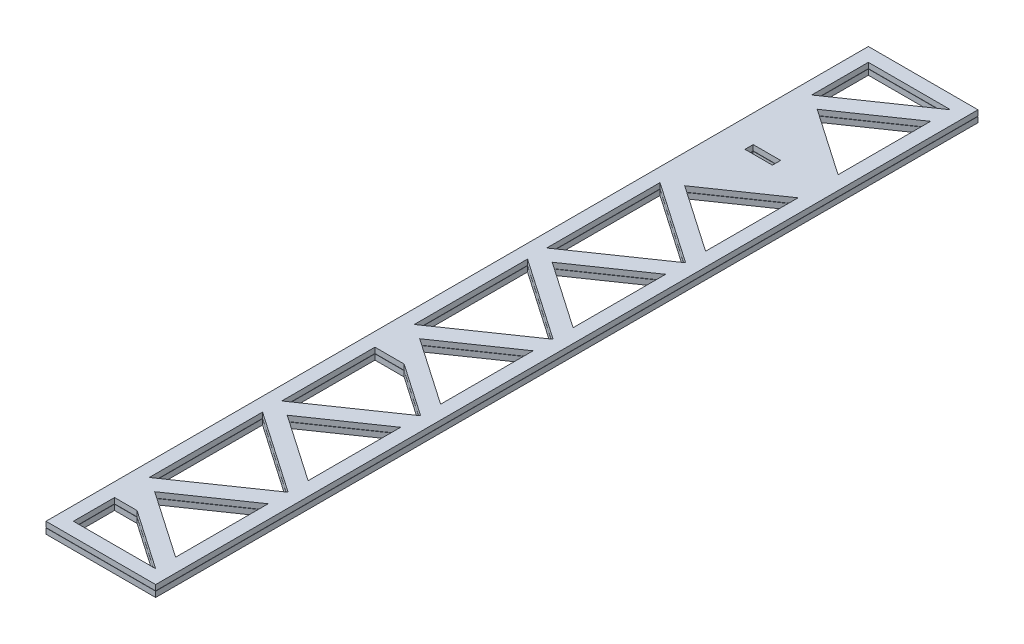
SolidWorks part; units mm, degrees
material "轻木"
ref_plane "前视基准面" through (0, 0, 0) normal (0, 0, 1) x (1, 0, 0)
ref_plane "上视基准面" through (0, 0, 0) normal (0, 1, 0) x (1, 0, 0)
ref_plane "右视基准面" through (0, 0, 0) normal (1, 0, 0) x (0, 0, -1)
other "Configuration Table"
sketch "草图2" plane through (0, 0, 762.01) normal (0, 0, 1) x (1, 0, 0)
  line L0 (130.7876, -3.3397) -> (130.7876, -3.4397) construction
  line L1 (130.7876, -1.3397) -> (170.7876, -1.3397)
  line L2 (130.7876, -1.3397) -> (130.7876, -3.3397)
  line L3 (130.7876, -3.3397) -> (170.7876, -3.3397)
  line L4 (170.7876, -1.3397) -> (170.7876, -3.3397)
  line L5 (130.7876, -3.4397) -> (170.7876, -3.4397)
  line L6 (130.7876, -3.4397) -> (130.7876, -5.4397)
  line L7 (130.7876, -5.4397) -> (170.7876, -5.4397)
  line L8 (170.7876, -3.4397) -> (170.7876, -5.4397)
  point P4 (130.7876, -3.3897)
  dimension "D1" = 2
  dimension "D2" = 40
  dimension "D3" = 2
  dimension "D4" = 40
  dimension "D5" = 0.1
extrude "凸台-拉伸1" add sketch "草图2" along normal blind 300
sketch "草图3" plane through (0, -1.3397, 0) normal (0, 1, 0) x (1, 0, 0)
  line L0 (165.7876, -1057.01) -> (165.7876, -767.01)
  line L1 (165.7876, -767.01) -> (135.7876, -767.01)
  line L2 (135.7876, -767.01) -> (135.7876, -1057.01)
  line L3 (135.7876, -1057.01) -> (165.7876, -1057.01)
  line L4 (170.7876, -762.01) -> (130.7876, -762.01)
  line L5 (130.7876, -762.01) -> (130.7876, -1062.01)
  line L6 (130.7876, -1062.01) -> (170.7876, -1062.01)
  line L7 (170.7876, -1062.01) -> (170.7876, -762.01)
  line L8 (170.7876, -762.01) -> (130.7876, -762.01)
  line L9 (130.7876, -762.01) -> (130.7876, -1062.01)
  line L10 (130.7876, -1062.01) -> (170.7876, -1062.01)
  line L11 (170.7876, -1062.01) -> (170.7876, -762.01)
  line L12 (170.7876, -912.01) -> (130.7876, -912.01) construction
  line L13 (165.7876, -1057.01) -> (135.7876, -1036.3433)
  line L14 (135.7876, -1029.3433) -> (165.7876, -1008.6767)
  line L15 (165.7876, -1008.6767) -> (135.7876, -988.01)
  line L16 (135.7876, -981.01) -> (165.7876, -960.3433)
  line L17 (165.7876, -960.3433) -> (135.7876, -939.6767)
  line L18 (135.7876, -932.6767) -> (165.7876, -912.01)
  line L19 (165.7876, -1049.7241) -> (141.2833, -1032.8433)
  line L20 (141.2833, -1032.8433) -> (165.7876, -1015.9626)
  line L21 (165.7876, -953.0574) -> (141.2833, -936.1767)
  line L22 (141.2833, -984.51) -> (165.7876, -967.6292)
  line L23 (141.2833, -936.1767) -> (163.0951, -921.1507) construction
  line L24 (141.2833, -936.1767) -> (165.7876, -919.2959)
  line L25 (130.707, -936.1767) -> (159.6913, -916.2097) construction
  line L26 (169.1914, -1052.069) -> (141.2833, -1032.8433) construction
  line L27 (165.7876, -1001.3908) -> (141.2833, -984.51)
  line L28 (176.3639, -1008.6767) -> (141.2833, -984.51) construction
  line L29 (176.3639, -960.3433) -> (141.2833, -936.1767) construction
  line L30 (141.2833, -1032.8433) -> (176.3639, -1008.6767) construction
  line L31 (165.7876, -960.3433) -> (130.707, -936.1767) construction
  line L32 (141.2833, -984.51) -> (176.3639, -960.3433) construction
  line L33 (130.707, -984.51) -> (165.7876, -960.3433) construction
  line L34 (165.7876, -1008.6767) -> (130.707, -984.51) construction
  line L35 (130.707, -1032.8433) -> (165.7876, -1008.6767) construction
  line L36 (165.7876, -1057.01) -> (130.707, -1032.8433) construction
  line L37 (141.2833, -887.8433) -> (165.7876, -904.7241)
  line L38 (135.7876, -891.3433) -> (165.7876, -912.01)
  line L39 (165.7876, -870.9626) -> (141.2833, -887.8433)
  line L40 (165.7876, -863.6767) -> (135.7876, -884.3433)
  line L41 (135.7876, -843.01) -> (165.7876, -863.6767)
  line L42 (141.2833, -839.51) -> (165.7876, -856.3908)
  line L43 (165.7876, -822.6292) -> (141.2833, -839.51)
  line L44 (165.7876, -815.3433) -> (135.7876, -836.01)
  line L45 (135.7876, -794.6767) -> (165.7876, -815.3433)
  line L46 (165.7876, -767.01) -> (135.7876, -787.6767)
  line L47 (165.7876, -774.2959) -> (141.2833, -791.1767)
  line L48 (141.2833, -791.1767) -> (165.7876, -808.0574)
  line L49 (144.0134, -1042.01) -> (135.7876, -1042.01)
  line L50 (146.4328, -947.01) -> (135.7876, -947.01)
  dimension "D4" = 7
  dimension "D5" = 15
  dimension "D6" = 95
  dimension "D1" = 0
  dimension "D2" = 5
  dimension "D3" = 6
extrude "切除-拉伸1" cut sketch "草图3" against normal through all contours L46 L1 L2 | L47 L48 L0 | L41 L2 L40 | L0 L39 L37 | L38 L2 L18 | L24 L21 L0 | L16 L17 L2 | L27 L0 L22 | L14 L15 L2 | L20 L19 L0 | L3 L13 L2 | L0 L43 L42 region at (146.3776, -1.3397, 1050.9341) region at (157.6195, -1.3397, 1032.8433) region at (145.7876, -1.3397, 1008.6767) region at (157.6195, -1.3397, 984.51) region at (146.221, -1.3397, 961.4034) region at (157.6195, -1.3397, 936.1767) region at (145.7876, -1.3397, 912.01) region at (157.6195, -1.3397, 887.8433) region at (145.7876, -1.3397, 863.6767) region at (157.6195, -1.3397, 839.51) region at (145.7876, -1.3397, 773.8989) region at (157.6195, -1.3397, 791.1767)
sketch "草图4" plane through (0, -5.4397, 0) normal (0, -1, 0) x (1, 0, 0)
  line L0 (130.7876, 1062.01) -> (130.7876, 762.01) construction
  line L1 (140.7876, 817.01) -> (150.7876, 817.01)
  line L2 (140.7876, 817.01) -> (140.7876, 814.01)
  line L3 (140.7876, 814.01) -> (150.7876, 814.01)
  line L4 (150.7876, 817.01) -> (150.7876, 814.01)
  line L5 (130.7876, 762.01) -> (170.7876, 762.01) construction
  dimension "D1" = 10
  dimension "D2" = 3
  dimension "D3" = 10
  dimension "D4" = 52
extrude "切除-拉伸2" cut sketch "草图4" against normal through all
